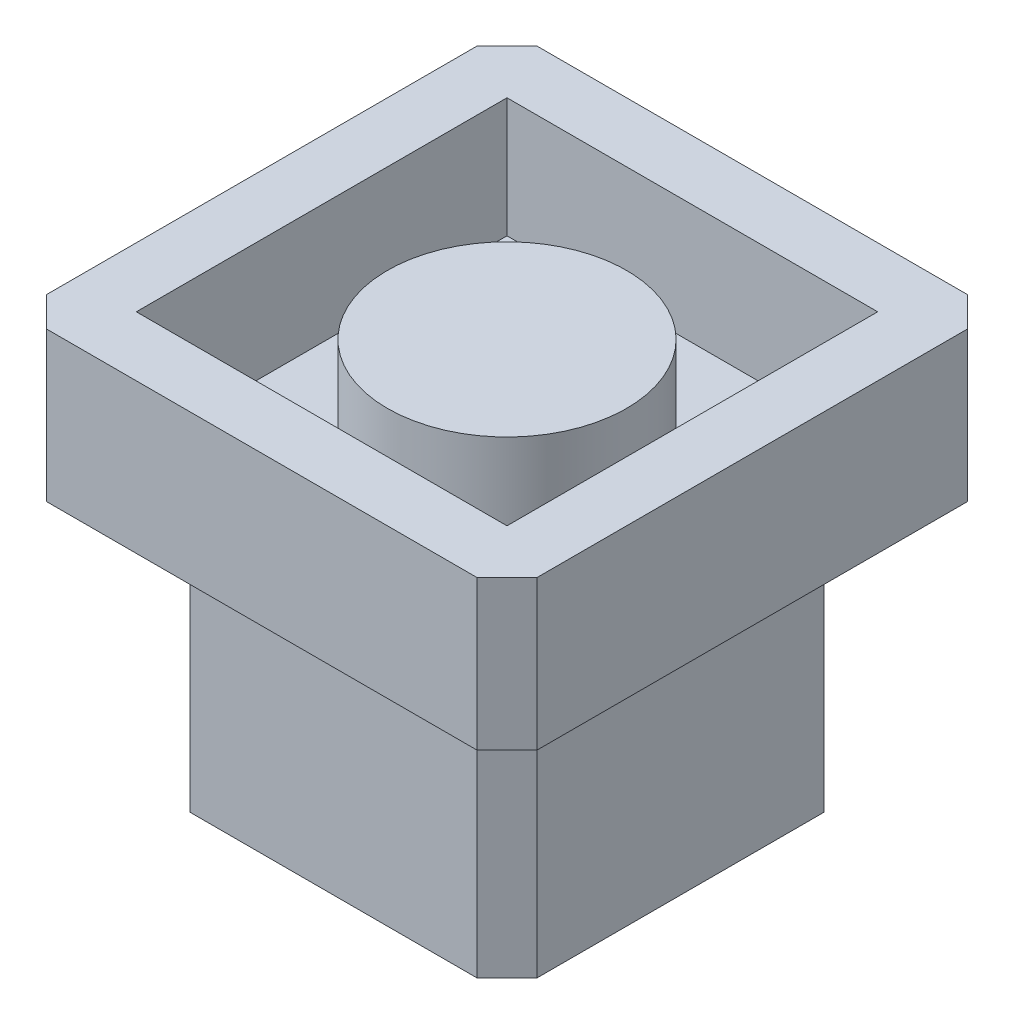
SolidWorks part; units mm, degrees
ref_plane "Front Plane" through (0, 0, 0) normal (0, 0, 1) x (1, 0, 0)
ref_plane "Top Plane" through (0, 0, 0) normal (0, 1, 0) x (1, 0, 0)
ref_plane "Right Plane" through (0, 0, 0) normal (1, 0, 0) x (0, 0, -1)
sketch "Sketch1" plane through (0, 0, 0) normal (0, 1, 0) x (1, 0, 0)
  line L0 (-4.1, 4.1) -> (-4.1, -4.1)
  line L1 (-3.1, 3.1) -> (3.1, 3.1)
  line L2 (-3.1, 3.1) -> (-3.1, -3.1)
  line L3 (-3.1, -3.1) -> (3.1, -3.1)
  line L4 (3.1, 3.1) -> (3.1, -3.1)
  line L5 (-3.1, 3.1) -> (3.1, -3.1) construction
  line L6 (-3.1, -3.1) -> (3.1, 3.1) construction
  line L7 (-4.1, -4.1) -> (4.1, -4.1)
  line L8 (4.1, 4.1) -> (4.1, -4.1)
  line L9 (-4.1, 4.1) -> (4.1, 4.1)
  circle A1 centre (0, 0) radius 2
  dimension "D1" = 4
  dimension "D2" = 6.2
  dimension "D3" = 1
extrude "Boss-Extrude1" add sketch "Sketch1" along normal blind 1.6 contours A1 region at (0, 0, 0)
extrude "Boss-Extrude2" add sketch "Sketch1<3>" along normal blind 2 separate body contours L9 L0 L7 L8 L1 L4 L3 L2 region at (0, 0, -3.984)
sketch "Sketch1<3>" plane through (0, 0, 0) normal (0, 1, 0) x (1, 0, 0) same geometry as "Sketch1"
extrude "Boss-Extrude3" add sketch "Sketch1<4>" against normal blind 0.5 contours L9 L0 L7 L8 L1 L4 L3 L2 | L4 L1 L2 L3 A1 | A1 region at (0, 0, -3.984) region at (0, 0, -3.0123) region at (0, 0, 0)
sketch "Sketch1<4>" plane through (0, 0, 0) normal (0, 1, 0) x (1, 0, 0) same geometry as "Sketch1"
sketch "Sketch3" plane through (0, -0.5, 0) normal (0, -1, 0) x (1, 0, 0)
  line L1 (-2.9, 2.9) -> (2.9, 2.9)
  line L2 (-2.9, 2.9) -> (-2.9, -2.9)
  line L3 (-2.9, -2.9) -> (2.9, -2.9)
  line L4 (2.9, 2.9) -> (2.9, -2.9)
  line L5 (-2.9, 2.9) -> (2.9, -2.9) construction
  line L6 (-2.9, -2.9) -> (2.9, 2.9) construction
  point P0 (0, 0)
  dimension "D1" = 5.8
  dimension "D2" = 5.8
extrude "Boss-Extrude4" add sketch "Sketch3" along normal blind 4.5
chamfer "Chamfer1" distance 0.5 angle 45 8 edges at (-4.1, 0.75, -4.1) (4.1, 0.75, -4.1) (-4.1, 0.75, 4.1) (4.1, 0.75, 4.1) (-2.9, -2.75, 2.9) (2.9, -2.75, 2.9) (-2.9, -2.75, -2.9) (2.9, -2.75, -2.9)
sketch "Sketch4" plane through (0, -5, 0) normal (0, -1, 0) x (1, 0, 0)
  text T1 "S\r\n"
extrude "Cut-Extrude1" cut sketch "Sketch4" against normal blind 0.2
